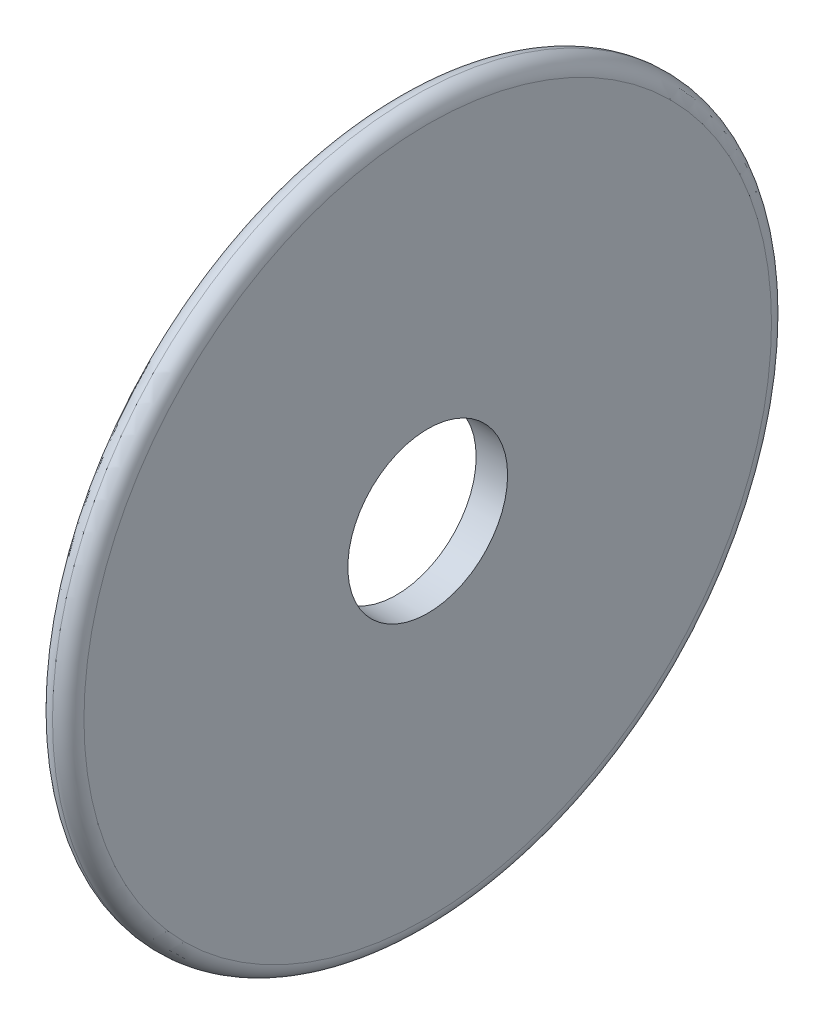
SolidWorks part; units mm, degrees
material "6061 Alloy"
ref_plane "Front Plane" through (0, 0, 0) normal (0, 0, 1) x (1, 0, 0)
ref_plane "Top Plane" through (0, 0, 0) normal (0, 1, 0) x (1, 0, 0)
ref_plane "Right Plane" through (0, 0, 0) normal (1, 0, 0) x (0, 0, -1)
sketch "Sketch1" plane through (0, 0, 0) normal (1, 0, 0) x (0, 0, -1)
  circle A0 centre (0, 0) radius 57.15
  dimension "D1" = 114.3
extrude "Boss-Extrude1" add sketch "Sketch1" along normal blind 5
sketch "Sketch2" plane through (5, 0, 0) normal (1, 0, 0) x (0, 0, -1)
  circle A0 centre (0, 0) radius 12.7
  dimension "D1" = 25.4
extrude "Cut-Extrude1" cut sketch "Sketch2" against normal through all
fillet "Fillet1" radius 2.5 2 edges at (0, 0, -57.15) (5, 0, -57.15)
